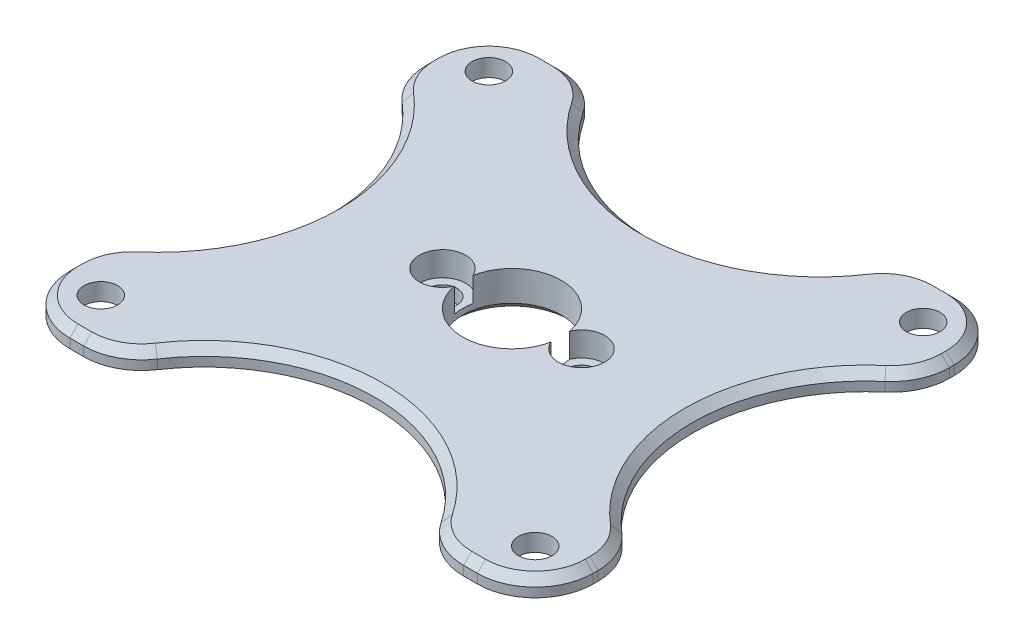
SolidWorks part; units mm, degrees
ref_plane "Front Plane" through (0, 0, 0) normal (0, 0, 1) x (1, 0, 0)
ref_plane "Top Plane" through (0, 0, 0) normal (0, 1, 0) x (1, 0, 0)
ref_plane "Right Plane" through (0, 0, 0) normal (1, 0, 0) x (0, 0, -1)
sketch "Sketch1" plane through (0, 0, 0) normal (0, 1, 0) x (1, 0, 0)
  circle A0 centre (0, 0) radius 8.75
  circle A1 centre (0, 0) radius 4.25
  circle A2 centre (0, 0) radius 6 construction
  circle A3 centre (-6, 0) radius 1.25
  circle A4 centre (6, 0) radius 1.25
  dimension "D1" = 17.5
  dimension "D2" = 8.5
  dimension "D3" = 2.5
  dimension "D4" = 12
extrude "Boss-Extrude1" add sketch "Sketch1" along normal blind 1.8
sketch "Sketch2" plane through (0, 1.8, 0) normal (0, 1, 0) x (1, 0, 0)
  circle A0 centre (-6, 0) radius 2
  circle A1 centre (6, 0) radius 2
  dimension "D1" = 4
extrude "Cut-Extrude1" cut sketch "Sketch2" against normal blind 0.6
sketch "Sketch3" plane through (0, 1.8, 0) normal (0, -1, 0) x (1, 0, 0)
  line L0 (-12.0837, 0) -> (12.0837, 0) construction
  line L1 (-18.75, -16.75) -> (18.75, -16.75) construction
  line L2 (-18.75, -16.75) -> (-18.75, 16.75) construction
  line L3 (-18.75, 16.75) -> (18.75, 16.75) construction
  line L4 (18.75, -16.75) -> (18.75, 16.75) construction
  line L5 (-18.75, -16.75) -> (18.75, 16.75) construction
  line L6 (-18.75, 16.75) -> (18.75, -16.75) construction
  line L7 (-22.5929, -20.5805) -> (-13.4662, -20.5805)
  line L8 (-22.5929, -20.5805) -> (-22.5929, -12.645)
  line L9 (-22.5929, 20.5805) -> (-13.4662, 20.5805)
  line L10 (22.5929, -20.5805) -> (22.5929, -12.645)
  line L11 (-22.5929, -20.5805) -> (22.5929, 20.5805) construction
  line L12 (-22.5929, 20.5805) -> (22.5929, -20.5805) construction
  line L13 (0, 12.2133) -> (0, -11.1132) construction
  line L14 (13.4662, -20.5805) -> (22.5929, -20.5805)
  line L15 (22.5929, 12.645) -> (22.5929, 20.5805)
  line L16 (13.4662, 20.5805) -> (22.5929, 20.5805)
  line L17 (-22.5929, 12.645) -> (-22.5929, 20.5805)
  circle A0 centre (18.75, 16.75) radius 1.45
  circle A1 centre (18.75, -16.75) radius 1.45
  circle A2 centre (-18.75, -16.75) radius 1.45
  circle A3 centre (-18.75, 16.75) radius 1.45
  arc A4 (22.5929, 12.645) -> (22.5929, -12.645) centre (30.5325, 0) ccw
  arc A5 (13.4662, -20.5805) -> (-13.4662, -20.5805) centre (0, -26.581) ccw
  arc A6 (-22.5929, 12.645) -> (-22.5929, -12.645) centre (-30.5325, 0) cw
  arc A7 (13.4662, 20.5805) -> (-13.4662, 20.5805) centre (0, 26.581) cw
  arc A8 (-4.1719, -0.8111) -> (4.1719, -0.8111) centre (0, 0) ccw
  circle A9 centre (0, 0) radius 4.25 construction
  arc A10 (-4.1719, 0.8111) -> (-4.1719, -0.8111) centre (-6, 0) ccw
  arc A11 (4.1719, -0.8111) -> (4.1719, 0.8111) centre (6, 0) ccw
  arc A14 (-4.1719, 0.8111) -> (-4.1719, -0.8111) centre (-6, 0) ccw construction
  arc A15 (4.1719, 0.8111) -> (-4.1719, 0.8111) centre (0, 0) ccw
  point P0 (0, 0)
  point P6 (0, 0)
  dimension "D3" = 2.9
  dimension "D1" = 33.5
  dimension "D2" = 37.5
extrude "Boss-Extrude2" add sketch "Sketch3" against normal blind 1.5
fillet "Fillet1" radius 5 12 edges at (22.5929, 2.55, -12.645) (22.5929, 2.55, -20.5805) (-13.4662, 2.55, -20.5805) (-22.5929, 2.55, -20.5805) (13.4662, 2.55, -20.5805) (-22.5929, 2.55, -12.645) (-22.5929, 2.55, 12.645) (-13.4662, 2.55, 20.5805) (-22.5929, 2.55, 20.5805) (22.5929, 2.55, 12.645) (22.5929, 2.55, 20.5805) (13.4662, 2.55, 20.5805)
chamfer "Chamfer1" distance 0.7 angle 45 2 edges at (0, 0, 4.25) (0, 0, 8.75)
chamfer "Chamfer2" distance 0.7 angle 45 24 edges at (0, 3.3, -11.8384) (14.0412, 3.3, -19.9924) (-14.0412, 3.3, -19.9924) (16.9934, 3.3, -20.5805) (-16.9934, 3.3, -20.5805) (21.1285, 3.3, -19.116) (-21.1285, 3.3, -19.116) (22.5929, 3.3, -15.37) (-22.5929, 3.3, -15.37) (22.1333, 3.3, -13.0655) (-22.1333, 3.3, -13.0655) (15.6016, 3.3, 0) (-15.6016, 3.3, 0) (22.1333, 3.3, 13.0655) (-22.1333, 3.3, 13.0655) (22.5929, 3.3, 15.37) (-22.5929, 3.3, 15.37) (21.1285, 3.3, 19.116) (-21.1285, 3.3, 19.116) (16.9934, 3.3, 20.5805) (-16.9934, 3.3, 20.5805) (14.0412, 3.3, 19.9924) (-14.0412, 3.3, 19.9924) (0, 3.3, 11.8384)
